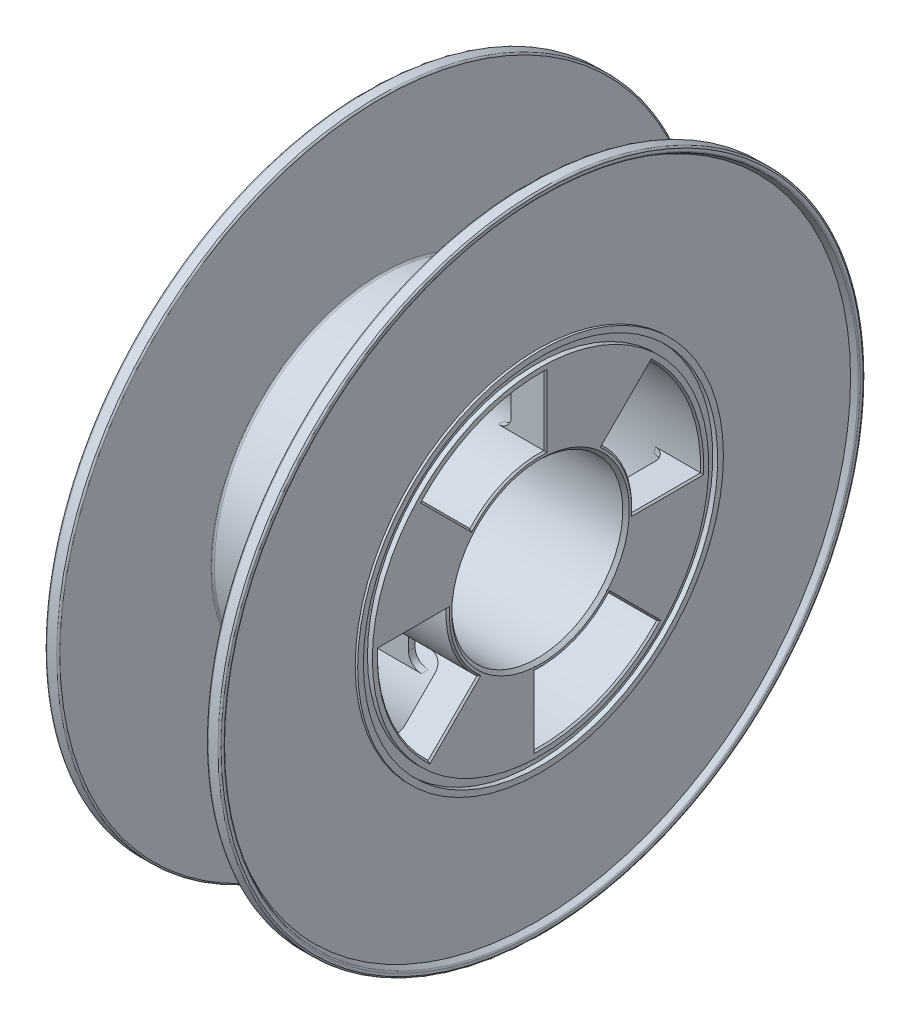
SolidWorks part; units mm, degrees
material "PA Type 6"
ref_plane "Front" through (0, 0, 0) normal (0, 0, 1) x (1, 0, 0)
ref_plane "Top" through (0, 0, 0) normal (0, 1, 0) x (1, 0, 0)
ref_plane "Right" through (0, 0, 0) normal (1, 0, 0) x (0, 0, -1)
sketch "Sketch1" plane through (0, 0, 0) normal (0, 0, 1) x (1, 0, 0)
  line L0 (0, 83.9129) -> (0, 0) construction
  line L1 (0, 0) -> (86.5967, 0) construction
  line L2 (-25.25, 26.25) -> (25.25, 26.25)
  line L3 (25.25, 26.25) -> (26.25, 27.25)
  line L4 (26.25, 27.25) -> (26.25, 28.5)
  line L5 (26.25, 28.5) -> (-26.25, 28.5)
  line L6 (-26.25, 28.5) -> (-26.25, 27.25)
  line L7 (-26.25, 27.25) -> (-25.25, 26.25)
  line L8 (-26.25, 49.625) -> (26.25, 49.625)
  line L9 (26.25, 49.625) -> (26.25, 51.625)
  line L10 (26.25, 51.625) -> (24.75, 51.625)
  line L11 (24.75, 51.625) -> (24.75, 54.375)
  line L12 (24.75, 54.375) -> (26.25, 54.375)
  line L13 (26.25, 54.375) -> (26.25, 56.125)
  line L14 (26.25, 56.125) -> (25.5, 56.125)
  line L15 (25.5, 56.125) -> (25, 96.4)
  line L16 (25, 96.4) -> (26.75, 97.4)
  line L17 (26.75, 97.4) -> (26.75, 99)
  line L18 (26.75, 99) -> (22.75, 99)
  line L19 (22.75, 99) -> (22.75, 51.625)
  line L20 (22.75, 51.625) -> (-22.75, 51.625)
  line L21 (-22.75, 99) -> (-22.75, 51.625)
  line L22 (-26.75, 99) -> (-22.75, 99)
  line L23 (-26.75, 97.4) -> (-26.75, 99)
  line L24 (-25, 96.4) -> (-26.75, 97.4)
  line L25 (-25.5, 56.125) -> (-25, 96.4)
  line L26 (-26.25, 56.125) -> (-25.5, 56.125)
  line L27 (-26.25, 54.375) -> (-26.25, 56.125)
  line L28 (-24.75, 54.375) -> (-26.25, 54.375)
  line L29 (-24.75, 51.625) -> (-24.75, 54.375)
  line L30 (-26.25, 51.625) -> (-24.75, 51.625)
  line L31 (-26.25, 49.625) -> (-26.25, 51.625)
  dimension "D1" = 52.5
  dimension "D2" = 45
  dimension "D3" = 52.5
  dimension "D4" = 1
  dimension "D5" = 2.25
  dimension "D6" = 49.625
  dimension "D7" = 2
  dimension "D8" = 1.75
  dimension "D9" = 6.5
  dimension "D10" = 1.5
  dimension "D11" = 53.5
  dimension "D12" = 0.75
  dimension "D13" = 1.75
  dimension "D14" = 2.6
  dimension "D15" = 198
  dimension "D16" = 1.6
  dimension "D17" = 45.5
revolve "Revolve1" add sketch "Sketch1" angle 360 about L1
fillet "Fillet1" radius 0.5 8 edges at (-26.75, 0, 97.4) (-26.75, 0, 99) (26.75, 0, 97.4) (26.75, 0, 99) (22.75, 0, 99) (-22.75, 0, 99) (-22.75, 0, 51.625) (22.75, 0, 51.625)
sketch "Sketch2" plane through (-26.25, 0, 0) normal (-1, 0, 0) x (0, 0, 1)
  line L0 (0, 56.125) -> (0, -56.125) construction
  line L1 (-56.125, 0) -> (56.125, 0) construction
  line L2 (2.5, 27.1351) -> (2.5, 50.1351)
  line L3 (0, 0) -> (39.6864, 39.6864) construction
  line L4 (17.4196, 20.9552) -> (33.6831, 37.2186)
  circle A0 centre (0, 0) radius 56.125 construction
  circle A1 centre (0, 0) radius 56.125 construction
  circle A4 centre (0, 0) radius 27.25 construction
  dimension "D1" = 2.5
  dimension "D2" = 45
  dimension "D3" = 2.5
  dimension "D4" = 23
extrude "Extrude-Thin1" add sketch "Sketch2" against normal blind 25 separate body thin thin type mid plane wall 2
sketch "Sketch5" plane through (26.25, 0, 0) normal (1, 0, 0) x (0, 0, -1)
  line L0 (0, 56.125) -> (0, -56.125) construction
  line L1 (0, 56.125) -> (0, -56.125) construction
  line L2 (2.5, 27.1351) -> (2.5, 50.1351)
  line L3 (-2.5, 27.1351) -> (-2.5, 50.1351) construction
  line L4 (-37.2186, 33.6831) -> (-20.9552, 17.4196)
  line L8 (0, 0) -> (-39.6864, 39.6864) construction
  line L9 (0, 0) -> (-39.6864, 39.6864) construction
  line L11 (-17.4196, 20.9552) -> (-33.6831, 37.2186) construction
  circle A0 centre (0, 0) radius 27.25 construction
extrude "Extrude-Thin2" add sketch "Sketch5" against normal blind 25 separate body thin thin type mid plane wall 2
pattern_circular "CirPattern1" count 4 over 360 about axis through (0, 0, 0) along (-1, 0, 0) of bodies 119 120 104 105
combine bodies "Combine1" operation type add bodies to combine 107 110 125 104 122 102 105 106 109 119 124 121 101 120 108 111 126 123
sketch "Sketch3" plane through (0, 0, 0) normal (0, 0, 1) x (1, 0, 0)
  line L0 (24.683, 0) -> (-34.9975, 0) construction
  line L1 (26.25, 28.5) -> (-26.25, 28.5) construction
  line L6 (26.25, 49.625) -> (-26.25, 49.625) construction
  line L7 (-11.75, 28.5) -> (11.75, 28.5)
  line L8 (-15.75, 32.5) -> (-15.75, 45.625)
  line L9 (-11.75, 49.625) -> (11.75, 49.625)
  line L10 (15.75, 32.5) -> (15.75, 45.625)
  line L15 (0, 0) -> (0, 49.625) construction
  arc A0 (11.75, 28.5) -> (15.75, 32.5) centre (11.75, 32.5) ccw
  arc A1 (-11.75, 28.5) -> (-15.75, 32.5) centre (-11.75, 32.5) cw
  arc A2 (-15.75, 45.625) -> (-11.75, 49.625) centre (-11.75, 45.625) cw
  arc A3 (11.75, 49.625) -> (15.75, 45.625) centre (11.75, 45.625) cw
  point P21 (-15.75, 28.5)
  dimension "D2" = 4
  dimension "D1" = 42
revolve "Cut-Revolve1" cut sketch "Sketch3" angle 360 about L0
sketch "Sketch4" plane through (26.25, 0, 0) normal (1, 0, 0) x (0, 0, -1)
  line L2 (22.4749, -17.5251) -> (37.4777, -32.5279)
  line L3 (49.5014, -3.5) -> (28.2843, -3.5)
  line L4 (22.4749, -17.5251) -> (37.4777, -32.5279)
  line L5 (49.5014, -3.5) -> (28.2843, -3.5)
  line L6 (3.5, 49.5014) -> (3.5, 28.2843)
  line L7 (17.5251, 22.4749) -> (32.5279, 37.4777)
  line L8 (3.5, 49.5014) -> (3.5, 28.2843)
  line L9 (17.5251, 22.4749) -> (32.5279, 37.4777)
  line L10 (-22.4749, 17.5251) -> (-37.4777, 32.5279)
  line L11 (-49.5014, 3.5) -> (-28.2843, 3.5)
  line L12 (-22.4749, 17.5251) -> (-37.4777, 32.5279)
  line L13 (-49.5014, 3.5) -> (-28.2843, 3.5)
  line L14 (-3.5, -49.5014) -> (-3.5, -28.2843)
  line L15 (-17.5251, -22.4749) -> (-32.5279, -37.4777)
  line L16 (-3.5, -49.5014) -> (-3.5, -28.2843)
  line L17 (-17.5251, -22.4749) -> (-32.5279, -37.4777)
  arc A4 (37.4777, -32.5279) -> (49.5014, -3.5) centre (0, 0) ccw
  arc A5 (22.4749, -17.5251) -> (28.2843, -3.5) centre (0, 0) ccw
  arc A6 (37.4777, -32.5279) -> (49.5014, -3.5) centre (0, 0) ccw
  arc A7 (22.4749, -17.5251) -> (28.2843, -3.5) centre (0, 0) ccw
  arc A8 (32.5279, 37.4777) -> (3.5, 49.5014) centre (0, 0) ccw
  arc A9 (17.5251, 22.4749) -> (3.5, 28.2843) centre (0, 0) ccw
  arc A10 (32.5279, 37.4777) -> (3.5, 49.5014) centre (0, 0) ccw
  arc A11 (17.5251, 22.4749) -> (3.5, 28.2843) centre (0, 0) ccw
  arc A12 (-37.4777, 32.5279) -> (-49.5014, 3.5) centre (0, 0) ccw
  arc A13 (-22.4749, 17.5251) -> (-28.2843, 3.5) centre (0, 0) ccw
  arc A14 (-37.4777, 32.5279) -> (-49.5014, 3.5) centre (0, 0) ccw
  arc A15 (-22.4749, 17.5251) -> (-28.2843, 3.5) centre (0, 0) ccw
  arc A16 (-17.5251, -22.4749) -> (-3.5, -28.2843) centre (0, 0) ccw
  arc A17 (-32.5279, -37.4777) -> (-3.5, -49.5014) centre (0, 0) ccw
  arc A18 (-17.5251, -22.4749) -> (-3.5, -28.2843) centre (0, 0) ccw
  arc A19 (-32.5279, -37.4777) -> (-3.5, -49.5014) centre (0, 0) ccw
  dimension "D1" = 0
  dimension "D2" = 0
  dimension "D3" = 0
  dimension "D4" = 0
extrude "Boss-Extrude1" add sketch "Sketch4" against normal blind 2
sketch "Sketch6" plane through (-26.25, 0, 0) normal (-1, 0, 0) x (0, 0, 1)
  line L3 (22.4749, -17.5251) -> (37.4777, -32.5279)
  line L4 (49.5014, -3.5) -> (28.2843, -3.5)
  line L5 (22.4749, -17.5251) -> (37.4777, -32.5279)
  line L6 (49.5014, -3.5) -> (28.2843, -3.5)
  line L8 (3.5, 49.5014) -> (3.5, 28.2843)
  line L9 (17.5251, 22.4749) -> (32.5279, 37.4777)
  line L10 (3.5, 49.5014) -> (3.5, 28.2843)
  line L11 (17.5251, 22.4749) -> (32.5279, 37.4777)
  line L12 (-22.4749, 17.5251) -> (-37.4777, 32.5279)
  line L13 (-49.5014, 3.5) -> (-28.2843, 3.5)
  line L14 (-22.4749, 17.5251) -> (-37.4777, 32.5279)
  line L15 (-49.5014, 3.5) -> (-28.2843, 3.5)
  line L16 (-17.5251, -22.4749) -> (-32.5279, -37.4777)
  line L17 (-3.5, -49.5014) -> (-3.5, -28.2843)
  line L18 (-17.5251, -22.4749) -> (-32.5279, -37.4777)
  line L19 (-3.5, -49.5014) -> (-3.5, -28.2843)
  arc A2 (37.4777, -32.5279) -> (49.5014, -3.5) centre (0, 0) ccw
  arc A3 (22.4749, -17.5251) -> (28.2843, -3.5) centre (0, 0) ccw
  arc A4 (37.4777, -32.5279) -> (49.5014, -3.5) centre (0, 0) ccw
  arc A5 (22.4749, -17.5251) -> (28.2843, -3.5) centre (0, 0) ccw
  arc A6 (17.5251, 22.4749) -> (3.5, 28.2843) centre (0, 0) ccw
  arc A7 (32.5279, 37.4777) -> (3.5, 49.5014) centre (0, 0) ccw
  arc A8 (17.5251, 22.4749) -> (3.5, 28.2843) centre (0, 0) ccw
  arc A9 (32.5279, 37.4777) -> (3.5, 49.5014) centre (0, 0) ccw
  arc A10 (-37.4777, 32.5279) -> (-49.5014, 3.5) centre (0, 0) ccw
  arc A11 (-22.4749, 17.5251) -> (-28.2843, 3.5) centre (0, 0) ccw
  arc A12 (-37.4777, 32.5279) -> (-49.5014, 3.5) centre (0, 0) ccw
  arc A13 (-22.4749, 17.5251) -> (-28.2843, 3.5) centre (0, 0) ccw
  arc A14 (-17.5251, -22.4749) -> (-3.5, -28.2843) centre (0, 0) ccw
  arc A15 (-32.5279, -37.4777) -> (-3.5, -49.5014) centre (0, 0) ccw
  arc A16 (-17.5251, -22.4749) -> (-3.5, -28.2843) centre (0, 0) ccw
  arc A17 (-32.5279, -37.4777) -> (-3.5, -49.5014) centre (0, 0) ccw
  dimension "D1" = 0
  dimension "D2" = 0
  dimension "D3" = 0
  dimension "D4" = 0
extrude "Boss-Extrude2" add sketch "Sketch6" against normal blind 2
chamfer "Chamfer1" distance 0.5 angle 45 32 edges at (26.25, -28.66, 26.5387) (26.25, -18.9907, 45.8475) (26.25, 1.5, 39.0314) (26.25, -10.9065, 26.3306) (26.25, -45.8475, -18.9907) (26.25, -26.5387, -28.66) (26.25, -26.3306, -10.9065) (26.25, -39.0314, 1.5) (26.25, 18.9907, -45.8475) (26.25, -1.5, -39.0314) (26.25, 10.9065, -26.3306) (26.25, 28.66, -26.5387) (26.25, 26.3306, 10.9065) (26.25, 39.0314, -1.5) (26.25, 26.5387, 28.66) (26.25, 45.8475, 18.9907) (-26.25, -45.8475, 18.9907) (-26.25, -26.5387, 28.66) (-26.25, -26.3306, 10.9065) (-26.25, -39.0314, -1.5) (-26.25, 28.66, 26.5387) (-26.25, 18.9907, 45.8475) (-26.25, -1.5, 39.0314) (-26.25, 10.9065, 26.3306) (-26.25, 26.3306, -10.9065) (-26.25, 39.0314, 1.5) (-26.25, 45.8475, -18.9907) (-26.25, 26.5387, -28.66) (-26.25, 1.5, -39.0314) (-26.25, -18.9907, -45.8475) (-26.25, -28.66, -26.5387) (-26.25, -10.9065, -26.3306)
